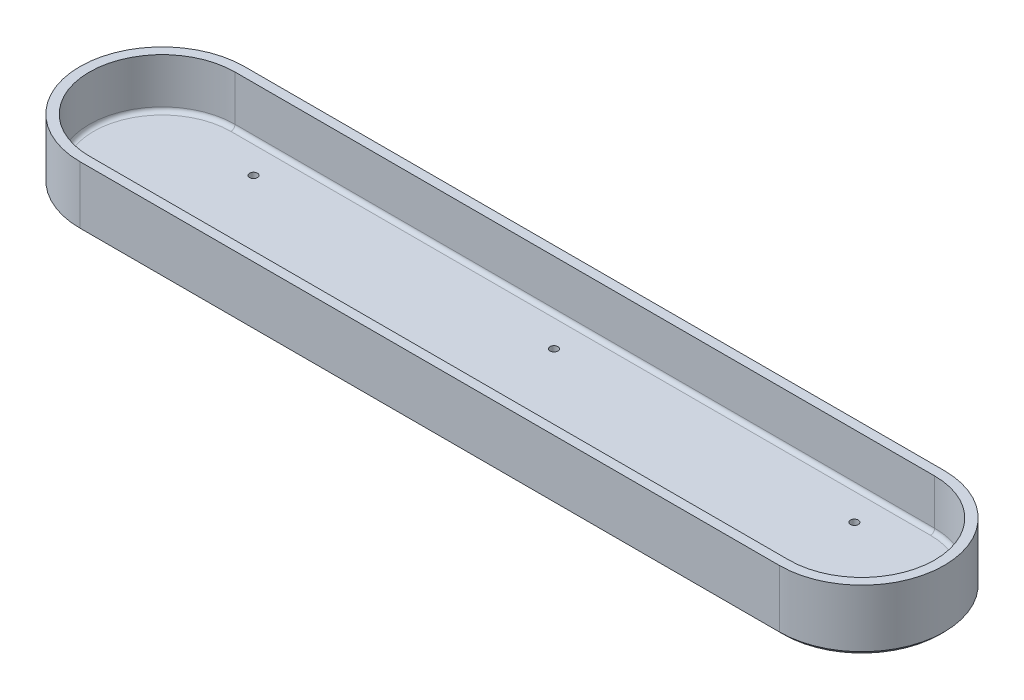
SolidWorks part; units mm, degrees
ref_plane "Front Plane" through (0, 0, 0) normal (0, 0, 1) x (1, 0, 0)
ref_plane "Top Plane" through (0, 0, 0) normal (0, 1, 0) x (1, 0, 0)
ref_plane "Right Plane" through (0, 0, 0) normal (1, 0, 0) x (0, 0, -1)
sketch "Sketch1" plane through (0, 0, 0) normal (0, 1, 0) x (1, 0, 0)
  line L0 (-107.95, 0) -> (107.95, 0) construction
  line L1 (0, -55.9739) -> (0, 55.9739) construction
  line L2 (-107.95, 22.479) -> (107.95, 22.479)
  line L3 (-107.95, -22.479) -> (107.95, -22.479)
  arc A0 (-107.95, 22.479) -> (-107.95, -22.479) centre (-107.95, 0) ccw
  arc A1 (107.95, 22.479) -> (107.95, -22.479) centre (107.95, 0) cw
  point P4 (0, 0)
  point P10 (0, 0)
  dimension "D2" = 44.958
  dimension "D1" = 215.9
extrude "MainBlock" add sketch "Sketch1" along normal blind 3.81
sketch "Sketch2" plane through (0, 0, 0) normal (0, -1, 0) x (1, 0, 0)
  line L0 (0, 0) -> (0, 50000) construction
  line L1 (-107.95, 25.4) -> (107.95, 25.4)
  line L2 (-107.95, -22.479) -> (107.95, -22.479)
  line L3 (107.95, 22.479) -> (-107.95, 22.479)
  line L5 (107.95, 22.479) -> (-107.95, 22.479)
  line L6 (-95.25, 0) -> (49904.75, 0) construction
  line L7 (107.95, -22.479) -> (-107.95, -22.479)
  line L8 (-107.95, -25.4) -> (107.95, -25.4)
  arc A0 (-107.95, 25.4) -> (-107.95, -25.4) centre (-107.95, 0) ccw
  arc A1 (107.95, 22.479) -> (107.95, -22.479) centre (107.95, 0) cw
  arc A2 (-107.95, 22.479) -> (-107.95, -22.479) centre (-107.95, 0) ccw
  arc A3 (107.95, -22.479) -> (107.95, 22.479) centre (107.95, 0) ccw
  arc A4 (-107.95, 22.479) -> (-107.95, -22.479) centre (-107.95, 0) ccw
  arc A6 (107.95, 25.4) -> (107.95, -25.4) centre (107.95, 0) cw
  point P0 (0, 22.479)
  point P15 (0, 25.4)
  point P16 (0, -22.479)
  point P19 (0, -25.4)
  dimension "2.1" = 50.8
  dimension "D1" = 0
extrude "Boss-Extrude1" add sketch "Sketch2" against normal blind 19.05
sketch "Sketch3" plane through (0, 0, 0) normal (0, -1, 0) x (1, 0, 0)
  line L0 (0, 0) -> (50000, 0) construction
  line L1 (0, 0) -> (0, 50000) construction
  line L2 (-107.95, 0.9216) -> (-107.95, 50000.9216) construction
  arc A0 (-107.95, 25.4) -> (-107.95, -25.4) centre (-107.95, 0) ccw construction
  arc A1 (-107.95, 25.4) -> (-107.95, -25.4) centre (-107.95, 0) ccw construction
  circle A2 centre (0, 12.954) radius 1.2065
  circle A3 centre (-92.71, 12.954) radius 1.2065
  circle A4 centre (92.71, 12.954) radius 1.2065
  circle A5 centre (92.71, -12.954) radius 1.2065
  circle A6 centre (-92.71, -12.954) radius 1.2065
  circle A7 centre (0, -12.954) radius 1.2065
  dimension "D1" = 2.413
  dimension "D4" = 2.413
  dimension "D2" = 12.954
  dimension "D3" = 12.954
  dimension "D5" = 15.24
extrude "Cut-Extrude1" cut sketch "Sketch3" against normal through all
fillet "Fillet1" radius 1.27 4 edges at (130.429, 3.81, 0) (0, 3.81, 22.479) (-130.429, 3.81, 0) (0, 3.81, -22.479)
chamfer "Chamfer1" distance 1.27 angle 45 4 edges at (0, 0, 25.4) (-133.35, 0, 0) (133.35, 0, 0) (0, 0, -25.4)
equation "\"D4@Sketch3\"=\"D1@Sketch3\""
